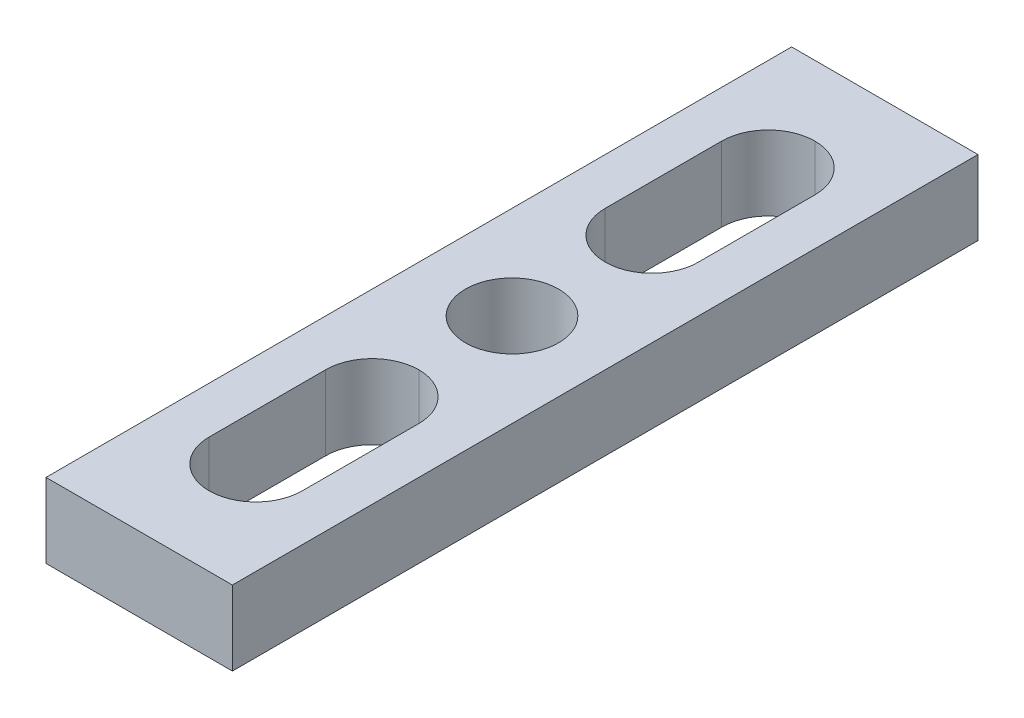
SolidWorks part; units mm, degrees
material "1060 Alloy"
ref_plane "Front Plane" through (0, 0, 0) normal (0, 0, 1) x (1, 0, 0)
ref_plane "Top Plane" through (0, 0, 0) normal (0, 1, 0) x (1, 0, 0)
ref_plane "Right Plane" through (0, 0, 0) normal (1, 0, 0) x (0, 0, -1)
sketch "Sketch1" plane through (0, 0, 0) normal (0, 0, 1) x (1, 0, 0)
  line L0 (55, 0) -> (-55, 0) construction
  line L1 (-12.7, 10.16) -> (12.7, 10.16)
  line L2 (-12.7, 10.16) -> (-12.7, 0)
  line L3 (-12.7, 0) -> (12.7, 0)
  line L4 (12.7, 10.16) -> (12.7, 0)
  line L5 (0, -55) -> (0, 55) construction
  dimension "D1" = 10.16
  dimension "D2" = 25.4
  dimension "D3" = 12.7
extrude "Boss-Extrude1" add sketch "Sketch1" along normal blind 101.6
sketch "Sketch2" plane through (0, 10.16, 0) normal (0, 1, 0) x (1, 0, 0)
  line L0 (0, -5.588) -> (0, 5.588) construction
  line L1 (-5.588, 0) -> (5.588, 0) construction
  circle A0 centre (0, -50.8) radius 6.35
  dimension "D1" = 50.8
extrude "Cut-Extrude1" cut sketch "Sketch2" against normal blind 88.9
ref_plane "Plane2" through (0, 0, 50.8) normal (0, 0, 1) x (1, 0, 0)
ref_plane "Plane3" through (0, 5.08, 0) normal (0, 1, 0) x (1, 0, 0)
sketch "Sketch5" plane through (0, 10.16, 0) normal (0, 1, 0) x (1, 0, 0)
  line L0 (12.7, -101.6) -> (12.7, 0) construction
  line L5 (6.35, -63.5) -> (-6.35, -63.5)
  line L6 (6.35, -63.5) -> (6.35, -92.075)
  line L7 (6.35, -92.075) -> (-6.35, -92.075)
  line L8 (-6.35, -63.5) -> (-6.35, -92.075)
  line L9 (-12.7, -101.6) -> (-12.7, 0) construction
  line L10 (12.7, -101.6) -> (-12.7, -101.6) construction
  line L11 (-5.588, -50.8) -> (5.588, -50.8) construction
  line L12 (-6.35, -38.1) -> (-6.35, -9.525)
  line L13 (6.35, -9.525) -> (-6.35, -9.525)
  line L14 (6.35, -38.1) -> (6.35, -9.525)
  line L15 (6.35, -38.1) -> (-6.35, -38.1)
  dimension "D1" = 6.35
  dimension "D2" = 6.35
  dimension "D3" = 9.525
  dimension "D4" = 28.575
extrude "Cut-Extrude3" cut sketch "Sketch5" against normal blind 15.875
mirror "Mirror1" [suppressed] about plane through (0, 5.08, 0) normal (0, 1, 0)
fillet "Fillet1" radius 6.35 8 edges at (-6.35, 5.08, 92.075) (-6.35, 5.08, 38.1) (-6.35, 5.08, 63.5) (-6.35, 5.08, 9.525) (6.35, 5.08, 9.525) (6.35, 5.08, 63.5) (6.35, 5.08, 92.075) (6.35, 5.08, 38.1)
